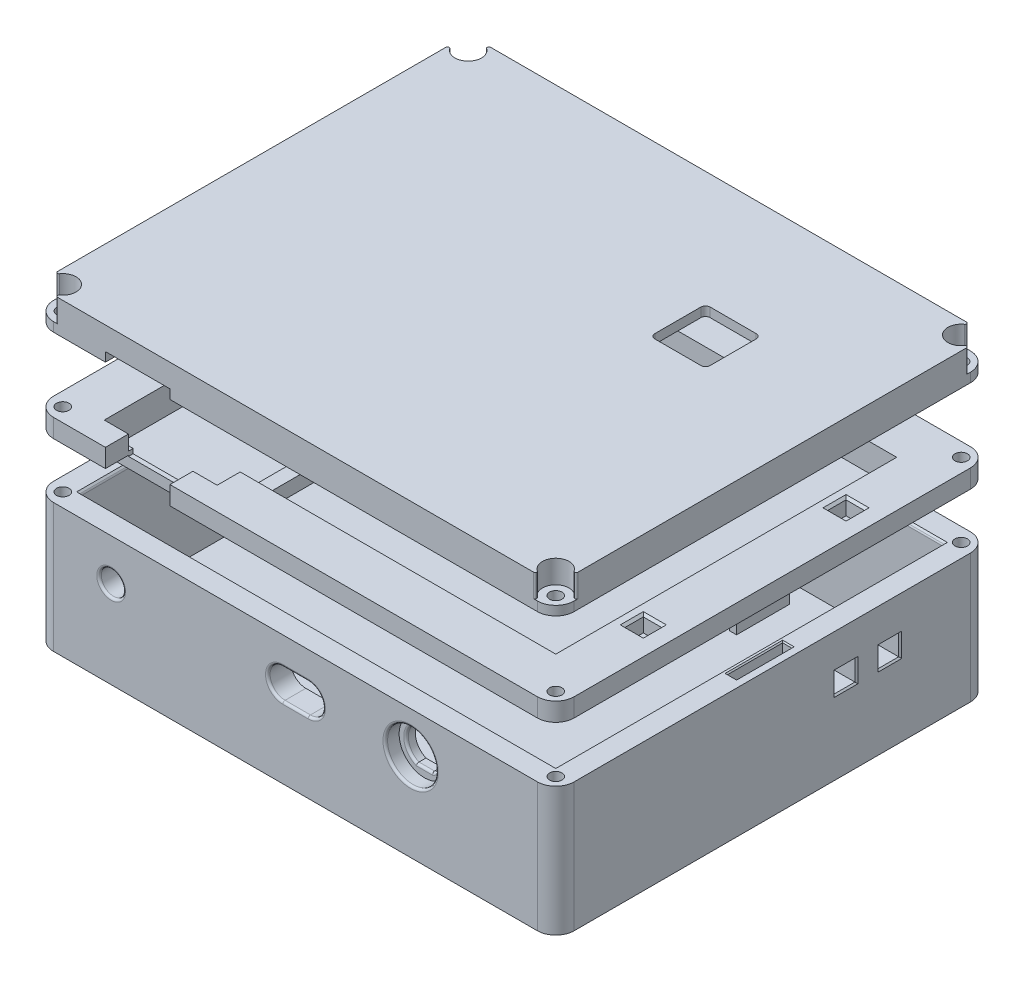
SolidWorks part; units mm, degrees
ref_plane "Front Plane" through (0, 0, 0) normal (0, 0, 1) x (1, 0, 0)
ref_plane "Top Plane" through (0, 0, 0) normal (0, 1, 0) x (1, 0, 0)
ref_plane "Right Plane" through (0, 0, 0) normal (1, 0, 0) x (0, 0, -1)
sketch "Sketch1" plane through (0, 0, 0) normal (0, 1, 0) x (1, 0, 0)
  line L0 (-1, 89) -> (104, 89)
  line L1 (0, 0) -> (103, 0)
  line L2 (0, 0) -> (0, 84)
  line L3 (0, 84) -> (103, 84)
  line L4 (103, 0) -> (103, 84)
  line L5 (108, -1) -> (108, 85)
  line L6 (-1, -5) -> (104, -5)
  line L7 (-5, -1) -> (-5, 85)
  line L8 (0, 0) -> (0, 13.5) construction
  line L9 (0, 84) -> (0, 72) construction
  line L10 (0, 0) -> (4, 0) construction
  line L11 (-5, 89) -> (108, 89) construction
  line L12 (108, -5) -> (108, 89) construction
  line L13 (-5, -5) -> (108, -5) construction
  line L14 (-5, -5) -> (-5, 89) construction
  line L15 (0, 13.5) -> (1.5, 13.5)
  line L20 (1.5, 13.5) -> (1.5, 0)
  line L21 (0, 72) -> (1.5, 72)
  line L22 (1.5, 72) -> (1.5, 84)
  line L23 (4, 0) -> (4, 1.5)
  line L24 (4, 1.5) -> (1.5, 1.5)
  arc A0 (104, 89) -> (108, 85) centre (104, 85) cw
  arc A1 (108, -1) -> (104, -5) centre (104, -1) cw
  arc A2 (-5, -1) -> (-1, -5) centre (-1, -1) ccw
  arc A3 (-5, 85) -> (-1, 89) centre (-1, 85) cw
  dimension "D7" = 4
  dimension "D1" = 103
  dimension "D2" = 84
  dimension "D4" = 13.5
  dimension "D5" = 12
  dimension "D6" = 4
  dimension "D8" = 1.5
  dimension "D9" = 1.5
  dimension "D10" = 1.5
  dimension "D3" = 5
extrude "Boss-Extrude1" add sketch "Sketch1" along normal blind 4 contours L0 A0 L5 A1 L6 A2 L7 A3
extrude "Boss-Extrude2" add sketch "Sketch1<3>" along normal blind 24 from surface contours A3 L7 A2 L6 A1 L5 A0 L0 L4 L1 L2 L3 region at (51.5, 0, -87.5301) starting at face at (51.5, 4, -42)
sketch "Sketch1<3>" plane through (0, 0, 0) normal (0, 1, 0) x (1, 0, 0) same geometry as "Sketch1"
extrude "Boss-Extrude3" add sketch "Sketch1<4>" along normal blind 8 from surface contours L21 L22 L3 L2 | L20 L15 L2 L1 | L23 L24 L20 L1 region at (0.75, 0, -6.75) region at (2.75, 0, -0.75) region at (0.75, 0, -78) starting at face at (51.5, 4, -42)
sketch "Sketch1<4>" plane through (0, 0, 0) normal (0, 1, 0) x (1, 0, 0) same geometry as "Sketch1"
chamfer "Chamfer1" distance 1 angle 45 6 edges at (0.75, 12, -13.5) (4, 12, -0.75) (2.75, 12, -1.5) (1.5, 12, -7.5) (0.75, 12, -72) (1.5, 12, -78)
sketch "Sketch2" plane through (0, 0, 0) normal (0, 0, 1) x (1, 0, 0)
  line L0 (51.5, 0) -> (51.5, 53.6645) construction
  line L1 (108, 0) -> (104, 0) construction
  line L2 (-1, 0) -> (104, 0) construction
  line L3 (-1, 0) -> (-5, 0) construction
  line L4 (108, 0) -> (104, 0) construction
  line L5 (-1, 0) -> (104, 0) construction
  line L6 (-1, 0) -> (-5, 0) construction
  line L7 (4, 4) -> (103, 4) construction
  line L8 (4, 4) -> (103, 4) construction
  line L9 (48.75, 18.7) -> (54.25, 18.7) construction
  line L10 (48.75, 21.95) -> (54.25, 21.95)
  line L11 (48.75, 15.45) -> (54.25, 15.45)
  line L12 (76.5, 4) -> (76.5, 15) construction
  line L13 (76.5, 22.625) -> (76.5, 15.375) construction
  line L14 (74.809, 22.625) -> (78.191, 22.625)
  line L15 (74.809, 15.375) -> (78.191, 15.375)
  arc A0 (48.75, 21.95) -> (48.75, 15.45) centre (48.75, 18.7) ccw
  arc A1 (54.25, 15.45) -> (54.25, 21.95) centre (54.25, 18.7) ccw
  arc A2 (74.809, 22.625) -> (74.809, 15.375) centre (76.5, 19) ccw
  circle A3 centre (76.5, 19) radius 5.5
  arc A4 (78.191, 22.625) -> (74.809, 22.625) centre (76.5, 19) ccw construction
  arc A5 (74.809, 15.375) -> (76.5, 15) centre (76.5, 19) ccw construction
  arc A6 (78.191, 15.375) -> (78.191, 22.625) centre (76.5, 19) ccw
  arc A7 (76.5, 15) -> (78.191, 15.375) centre (76.5, 19) ccw construction
  circle A8 centre (11.5, 19) radius 2.625
  point P6 (51.5, 18.7)
  point P15 (45.5, 18.7)
  point P16 (57.5, 18.7)
  point P26 (76.5, 19)
  point P28 (76.5, 22.625)
  point P31 (76.5, 15.375)
  dimension "D5" = 8
  dimension "D6" = 11
  dimension "D3" = 5.25
  dimension "D1" = 12
  dimension "D2" = 6.5
  dimension "D4" = 11
  dimension "D7" = 25
  dimension "D8" = 7.25
  dimension "D9" = 14.7
  dimension "D10" = 40
  dimension "D11" = 15
extrude "Cut-Extrude1" cut sketch "Sketch2" along normal blind 11 contours L11 A1 L10 A0 | L15 A6 L14 A2 | A8 region at (51.5, 18.7, 0) region at (76.5, 19, 0) region at (11.5, 19, 0)
extrude "Cut-Extrude2" cut sketch "Sketch2<3>" against normal blind 3 from surface contours A3 starting at face at (8.875, 19, 5)
sketch "Sketch2<3>" plane through (0, 0, 0) normal (0, 0, 1) x (1, 0, 0) same geometry as "Sketch2"
chamfer "Chamfer2" distance 0.5 angle 45 4 edges at (103, 28, -42) (51.5, 28, 0) (0, 28, -42) (51.5, 28, -84)
fillet "Fillet1" [suppressed] radius 5
fillet "Fillet2" radius 0.5 10 edges at (51.5, 21.95, 5) (57.5, 18.7, 5) (51.5, 15.45, 5) (71, 19, 5) (80.5, 19, 2) (76.5, 22.625, 2) (76.5, 15.375, 2) (72.5, 19, 2) (45.5, 18.7, 5) (8.875, 19, 5)
sketch "Sketch3" plane through (0, 28, 0) normal (0, 1, 0) x (1, 0, 0)
  line L0 (103, 0) -> (103, 84) construction
  line L1 (0, 0) -> (103, 0) construction
  line L2 (0, 0) -> (0, 84) construction
  line L3 (0, 84) -> (103, 84) construction
  line L4 (103, 0) -> (103, 84) construction
  line L5 (0, 0) -> (103, 0) construction
  line L6 (0, 0) -> (0, 84) construction
  line L7 (0, 84) -> (103, 84) construction
  line L8 (105, -2) -> (105, 86) construction
  line L9 (-2, 86) -> (105, 86) construction
  line L10 (-2, -2) -> (-2, 86) construction
  line L11 (-2, -2) -> (105, -2) construction
  line L12 (51.5, 86) -> (51.5, -2) construction
  line L13 (-1.25, 48) -> (-3.25, 48)
  line L14 (-1.25, 48) -> (-1.25, 36)
  line L15 (-1.25, 36) -> (-3.25, 36)
  line L16 (-3.25, 48) -> (-3.25, 36)
  line L17 (-1.25, 48) -> (-3.25, 36) construction
  line L18 (-1.25, 36) -> (-3.25, 48) construction
  line L19 (104.25, 36) -> (106.25, 36)
  line L20 (106.25, 48) -> (106.25, 36)
  line L21 (104.25, 48) -> (106.25, 48)
  line L22 (104.25, 48) -> (104.25, 36)
  circle A0 centre (-2, 86) radius 1.35
  circle A1 centre (105, 86) radius 1.35
  circle A2 centre (105, -2) radius 1.35
  circle A3 centre (-2, -2) radius 1.35
  point P12 (-2.25, 42)
  point P25 (-2, 42)
  dimension "D2" = 2.7
  dimension "D3" = 2.7
  dimension "D4" = 2.7
  dimension "D5" = 2.7
  dimension "D6" = 2
  dimension "D7" = 12
  dimension "D8" = 0.25
  dimension "D1" = 2
extrude "Cut-Extrude3" cut sketch "Sketch3" against normal blind 8 contours A3 | A2 | A1 | A0 region at (-2, 28, -86) region at (105, 28, -86) region at (105, 28, 2) region at (-2, 28, 2)
extrude "Cut-Extrude12" cut sketch "Sketch3<3>" against normal blind 4 contours L15 L16 L13 L14 | L19 L20 L21 L22
sketch "Sketch3<3>" plane through (0, 28, 0) normal (0, 1, 0) x (1, 0, 0) same geometry as "Sketch3"
ref_plane "Plane1" through (0, 40, 0) normal (0, 1, 0) x (1, 0, 0)
sketch "Sketch4" plane through (0, 40, 0) normal (0, 1, 0) x (1, 0, 0)
  line L4 (0, 0) -> (103, 0)
  line L5 (103, 0) -> (103, 84)
  line L6 (103, 84) -> (0, 84)
  line L7 (0, 84) -> (0, 0)
  line L8 (0, 0) -> (103, 0)
  line L9 (103, 0) -> (103, 84)
  line L10 (103, 84) -> (0, 84)
  line L11 (0, 84) -> (0, 0)
  line L12 (104, 89) -> (-1, 89)
  line L13 (108, -1) -> (108, 85)
  line L14 (-1, -5) -> (104, -5)
  line L15 (-5, 85) -> (-5, -1)
  line L16 (104, 89) -> (-1, 89)
  line L17 (108, -1) -> (108, 85)
  line L18 (-1, -5) -> (104, -5)
  line L19 (-5, 85) -> (-5, -1)
  line L23 (98, 79) -> (5, 79)
  line L25 (5, 79) -> (5, 5)
  line L26 (5, 5) -> (98, 5)
  line L28 (98, 5) -> (98, 79)
  line L29 (104.25, 36) -> (106.25, 36)
  line L30 (106.25, 36) -> (106.25, 48)
  line L31 (106.25, 48) -> (104.25, 48)
  line L32 (104.25, 48) -> (104.25, 36)
  line L33 (104.25, 36) -> (106.25, 36)
  line L34 (106.25, 36) -> (106.25, 48)
  line L35 (106.25, 48) -> (104.25, 48)
  line L36 (104.25, 48) -> (104.25, 36)
  line L37 (-1.25, 48) -> (-3.25, 48)
  line L38 (-1.25, 36) -> (-1.25, 48)
  line L39 (-3.25, 36) -> (-1.25, 36)
  line L40 (-3.25, 48) -> (-3.25, 36)
  line L41 (-1.25, 48) -> (-3.25, 48)
  line L42 (-1.25, 36) -> (-1.25, 48)
  line L43 (-3.25, 36) -> (-1.25, 36)
  line L44 (-3.25, 48) -> (-3.25, 36)
  line L45 (-1.5, 47.75) -> (-3, 47.75)
  line L46 (-3, 47.75) -> (-3, 36.25)
  line L47 (-3, 36.25) -> (-1.5, 36.25)
  line L48 (-1.5, 36.25) -> (-1.5, 47.75)
  line L49 (104.5, 36.25) -> (106, 36.25)
  line L50 (106, 36.25) -> (106, 47.75)
  line L51 (106, 47.75) -> (104.5, 47.75)
  line L52 (104.5, 47.75) -> (104.5, 36.25)
  line L53 (5, 5) -> (5, 0)
  line L54 (29.5, 5) -> (29.5, 0)
  circle A1 centre (-2, -2) radius 1.35
  circle A2 centre (-2, -2) radius 1.35
  circle A3 centre (105, -2) radius 1.35
  arc A4 (108, 85) -> (104, 89) centre (104, 85) ccw
  arc A5 (104, -5) -> (108, -1) centre (104, -1) ccw
  arc A6 (-5, -1) -> (-1, -5) centre (-1, -1) ccw
  arc A7 (-1, 89) -> (-5, 85) centre (-1, 85) ccw
  arc A8 (108, 85) -> (104, 89) centre (104, 85) ccw
  arc A9 (104, -5) -> (108, -1) centre (104, -1) ccw
  arc A10 (-5, -1) -> (-1, -5) centre (-1, -1) ccw
  arc A11 (-1, 89) -> (-5, 85) centre (-1, 85) ccw
  circle A12 centre (105, -2) radius 1.35
  circle A13 centre (105, 86) radius 1.35
  circle A14 centre (105, 86) radius 1.35
  circle A15 centre (-2, 86) radius 1.35
  circle A16 centre (-2, 86) radius 1.35
  dimension "D11" = 24.5
  dimension "D1" = 0
  dimension "D2" = 0
  dimension "D3" = 0
  dimension "D4" = 0
  dimension "D5" = 0
  dimension "D6" = 0
  dimension "D7" = 0
  dimension "D8" = 0
  dimension "D9" = 5
  dimension "D10" = 0.25
extrude "Boss-Extrude4" add sketch "Sketch4" along normal blind 4 separate body contours L16 A11 L19 A10 L18 A9 L17 A8 A16 A14 A12 L11 L10 L9 L8 L36 L35 L34 L33 L44 L41 L42 L43 A2 | L41 L44 L43 L42 | L35 L36 L33 L34 region at (106.7245, 40, -87.7245)
extrude "Boss-Extrude7" add sketch "Sketch4<5>" against normal blind 4 contours L46 L47 L48 L45 | L50 L51 L52 L49
sketch "Sketch4<5>" plane through (0, 40, 0) normal (0, 1, 0) x (1, 0, 0) same geometry as "Sketch4"
extrude "Boss-Extrude5" add sketch "Sketch4<3>" along normal mid plane 8 contours L10 L11 L8 L9 L28 L26 L25 L23 region at (1.3291, 40, -42)
sketch "Sketch4<3>" plane through (0, 40, 0) normal (0, 1, 0) x (1, 0, 0) same geometry as "Sketch4"
extrude "Boss-Extrude6" add sketch "Sketch4<4>" along normal blind 2 from surface contours L23 L25 L26 L28 starting at face at (47.1, 36, -33.6)
sketch "Sketch4<4>" plane through (0, 40, 0) normal (0, 1, 0) x (1, 0, 0) same geometry as "Sketch4"
sketch "Sketch5" plane through (0, 0, -5) normal (0, 0, 1) x (1, 0, 0)
  line L4 (5, 36) -> (29.5, 36)
  line L5 (29.5, 36) -> (29.5, 38)
  line L6 (29.5, 38) -> (5, 38)
  line L7 (5, 38) -> (5, 36)
  line L8 (5, 36) -> (29.5, 36)
  line L9 (29.5, 36) -> (29.5, 38)
  line L10 (29.5, 38) -> (5, 38)
  line L11 (5, 38) -> (5, 36)
  dimension "D1" = 0
extrude "Boss-Extrude8" add sketch "Sketch5" along normal up to surface (5 mm away) up to face at (2.5, 38, 0)
chamfer "Chamfer3" distance 1.5 angle 45 4 edges at (103, 36, -42) (51.5, 36, -84) (51.5, 36, 0) (0, 36, -42)
sketch "Sketch7" plane through (0, 0, 0) normal (0, 0, 1) x (1, 0, 0)
  line L0 (29.5, 40) -> (29.5, 38) construction
  line L2 (5, 40) -> (5, 38) construction
  line L3 (29.5, 40.7937) -> (29.5, 37.7398)
  line L4 (5, 37.7398) -> (29.5, 37.7398)
  line L5 (5, 40.7937) -> (5, 37.7398)
  line L6 (5, 40.7937) -> (29.5, 40.7937)
extrude "Boss-Extrude11" add sketch "Sketch7" against normal blind 1
sketch "Sketch6" plane through (0, 0, 0) normal (0, 0, 1) x (1, 0, 0)
  line L0 (5, 38) -> (29.5, 38) construction
  line L1 (5, 38) -> (29.5, 38) construction
  line L2 (17.25, 38) -> (17.25, 44.8184) construction
  line L3 (10.25, 39.8) -> (24.25, 39.8)
  line L4 (10.25, 41.5) -> (24.25, 41.5)
  line L5 (0, 37.5) -> (103, 37.5) construction
  line L6 (10.25, 41.5) -> (10.25, 39.8)
  line L7 (24.25, 41.5) -> (24.25, 39.8)
  line L8 (10.25, 41.5) -> (10.25, 44.8184)
  line L9 (10.25, 44.8184) -> (24.25, 44.8184)
  line L10 (24.25, 44.8184) -> (24.25, 41.5)
  point P7 (17.25, 39.8)
  point P10 (17.25, 41.5)
  dimension "D1" = 14
  dimension "D2" = 1.8
  dimension "D3" = 14
  dimension "D4" = 4
extrude "Cut-Extrude4" cut sketch "Sketch6" along normal mid plane 15 contours L10 L9 L8 L4 | L7 L3 L6 L4 region at (17.25, 43.1592, 0)
sketch "Sketch8" plane through (0, 38, 0) normal (0, 1, 0) x (1, 0, 0)
  line L0 (5, 44) -> (29.5, 44)
  line L1 (5, 79) -> (5, 1) construction
  line L2 (29.5, 1) -> (5, 1) construction
  line L3 (29.5, 44) -> (29.5, 5)
  line L4 (5, 48) -> (33.5, 48)
  line L5 (33.5, 48) -> (33.5, 5)
  line L7 (9.25, 52) -> (25.25, 52)
  line L8 (9.25, 52) -> (9.25, 56)
  line L9 (9.25, 56) -> (25.25, 56)
  line L10 (25.25, 52) -> (25.25, 56)
  point P16 (17.25, 52)
  point P17 (17.25, 44)
  line M11 (29.5, 5) -> (98, 5)
  line M14 (5, 79) -> (5, 1)
  dimension "D1" = 43
  dimension "D2" = 24.5
  dimension "D3" = 4
  dimension "D4" = 4
  dimension "D5" = 4
  dimension "D6" = 16
  dimension "D7" = 4
extrude "Boss-Extrude12" add sketch "Sketch8" along normal blind 3 contours L5 L4 L0 L3 M14 M11 region at (5.5159, 38, -46)
extrude "Cut-Extrude5" cut sketch "Sketch8<3>" against normal blind 3.5 contours L9 L10 L7 L8
sketch "Sketch8<3>" plane through (0, 38, 0) normal (0, 1, 0) x (1, 0, 0) same geometry as "Sketch8"
chamfer "Chamfer4" distance 1 angle 45 6 edges at (25.25, 38, -54) (17.25, 38, -56) (9.25, 38, -54) (17.25, 38, -52) (29.5, 41, -24.5) (17.25, 41, -44)
sketch "Sketch10" plane through (0, 38, 0) normal (0, 1, 0) x (1, 0, 0)
  line L0 (77.5, 64) -> (77.5, 52) construction
  line L1 (73.5, 64) -> (81.5, 64)
  line L2 (71.5, 62) -> (71.5, 54)
  line L3 (73.5, 52) -> (81.5, 52)
  line L4 (83.5, 62) -> (83.5, 54)
  line L5 (73.7129, 58) -> (81.5, 58) construction
  line L6 (82.5, 61.375) -> (84.5, 61.375)
  line L7 (82.5, 61.375) -> (82.5, 59.625)
  line L8 (82.5, 59.625) -> (84.5, 59.625)
  line L9 (84.5, 61.375) -> (84.5, 59.625)
  line L10 (82.5, 61.375) -> (84.5, 59.625) construction
  line L11 (82.5, 59.625) -> (84.5, 61.375) construction
  line L12 (82.5, 56.375) -> (84.5, 56.375)
  line L13 (84.5, 54.625) -> (84.5, 56.375)
  line L14 (82.5, 54.625) -> (84.5, 54.625)
  line L15 (82.5, 54.625) -> (82.5, 56.375)
  line L16 (72.5, 59.625) -> (70.5, 59.625)
  line L17 (70.5, 61.375) -> (70.5, 59.625)
  line L18 (72.5, 61.375) -> (70.5, 61.375)
  line L19 (72.5, 61.375) -> (72.5, 59.625)
  line L20 (72.5, 54.625) -> (72.5, 56.375)
  line L21 (72.5, 54.625) -> (70.5, 54.625)
  line L22 (70.5, 54.625) -> (70.5, 56.375)
  line L23 (72.5, 56.375) -> (70.5, 56.375)
  line L24 (51.5, 89) -> (51.5, -5) construction
  line L25 (-1, 89) -> (104, 89) construction
  line L26 (-1, -5) -> (104, -5) construction
  line L27 (-5, 42) -> (108, 42) construction
  line L28 (-5, -1) -> (-5, 85) construction
  line L29 (108, -1) -> (108, 85) construction
  line L30 (3, 18) -> (3, 22)
  line L31 (-1, 66) -> (3, 66)
  line L32 (-1, 66) -> (-1, 62)
  line L33 (-1, 62) -> (3, 62)
  line L34 (3, 66) -> (3, 62)
  line L35 (-1, 22) -> (3, 22)
  line L36 (-1, 18) -> (-1, 22)
  line L37 (-1, 18) -> (3, 18)
  line L39 (100, 18) -> (100, 22)
  line L40 (104, 18) -> (100, 18)
  line L41 (104, 18) -> (104, 22)
  line L42 (104, 22) -> (100, 22)
  line L43 (104, 62) -> (100, 62)
  line L44 (100, 66) -> (100, 62)
  line L45 (104, 66) -> (104, 62)
  line L46 (104, 66) -> (100, 66)
  circle A0 centre (77.5, 62.35) radius 0.8
  circle A1 centre (77.5, 53.65) radius 0.8
  arc A2 (71.5, 54) -> (73.5, 52) centre (73.5, 54) ccw
  arc A3 (81.5, 52) -> (83.5, 54) centre (81.5, 54) ccw
  arc A4 (83.5, 62) -> (81.5, 64) centre (81.5, 62) ccw
  arc A5 (71.5, 62) -> (73.5, 64) centre (73.5, 62) cw
  point P10 (77.5, 58)
  point P13 (71.5, 52)
  point P16 (83.5, 52)
  point P21 (71.5, 64)
  point P22 (83.5, 60.5)
  dimension "D3" = 1.6
  dimension "D4" = 1.6
  dimension "D7" = 2
  dimension "D1" = 12
  dimension "D2" = 12
  dimension "D5" = 8.7
  dimension "D6" = 4.35
  dimension "D8" = 1.75
  dimension "D9" = 2
  dimension "D10" = 2.5
  dimension "D11" = 4
  dimension "D12" = 4
  dimension "D13" = 20
  dimension "D14" = 48.5
  dimension "D15" = 20
  dimension "D16" = 10
extrude "Cut-Extrude6" cut sketch "Sketch10" against normal blind 3.5 from surface contours L36 L37 L30 L35 | L41 L42 L39 L40 | L45 L46 L44 L43 | L34 L31 L32 L33 region at (1, 38, -20) region at (1, 38, -64) region at (102, 38, -20) region at (102, 38, -64) starting at face at (41.4444, 44, -27.4444)
extrude "Boss-Extrude13" add sketch "Sketch10<3>" along normal blind 1.5 contours A5 L2 L18 L19 L16 L23 L20 L21 A2 L3 A3 L4 L14 L15 L12 L8 L7 L6 A4 L1 A1 A0 region at (77.5, 38, -58)
sketch "Sketch10<3>" plane through (0, 38, 0) normal (0, 1, 0) x (1, 0, 0) same geometry as "Sketch10"
extrude "Cut-Extrude7" cut sketch "Sketch10<4>" against normal up to next (2 mm away) contours L9 L6 L4 L8 | L7 L8 L4 L6 | L4 L14 L13 L12 | L15 L14 L4 L12 | L20 L23 L2 L21 | L2 L23 L22 L21 | L19 L18 L2 L16 | L17 L16 L19 L18 region at (72, 38, -60.5) region at (84, 38, -60.5) region at (83, 38, -60.5) region at (72, 38, -55.5) region at (71, 38, -55.5) region at (84, 38, -55.5) region at (83, 38, -55.5)
sketch "Sketch10<4>" plane through (0, 38, 0) normal (0, 1, 0) x (1, 0, 0) same geometry as "Sketch10"
fillet "Fillet3" radius 0.5 2 edges at (77.5, 39.5, -52.85) (77.5, 39.5, -61.55)
chamfer "Chamfer5" distance 0.5 angle 45 16 edges at (104, 44, -64) (102, 44, -62) (100, 44, -64) (102, 44, -66) (104, 44, -20) (102, 44, -18) (100, 44, -20) (102, 44, -22) (3, 44, -20) (1, 44, -18) (-1, 44, -20) (1, 44, -22) (1, 44, -62) (3, 44, -64) (-1, 44, -64) (1, 44, -66)
ref_plane "Plane3" through (0, 60, 0) normal (0, 1, 0) x (1, 0, 0)
sketch "Sketch12" plane through (0, 60, 0) normal (0, 1, 0) x (1, 0, 0)
  line L0 (29.5, 5) -> (5, 5)
  line L1 (24.25, -5) -> (10.25, -5)
  line L2 (100, 66) -> (100, 62) construction
  line L7 (72.5, 64) -> (82.5, 64)
  line L8 (71.5, 63) -> (71.5, 53)
  line L9 (72.5, 52) -> (82.5, 52)
  line L10 (83.5, 63) -> (83.5, 53)
  line L11 (71.5, 64) -> (83.5, 52) construction
  line L12 (71.5, 52) -> (83.5, 64) construction
  line L13 (100, 62) -> (104, 62) construction
  line L14 (24.25, 0) -> (24.25, -5)
  line L15 (24.25, -5) -> (104, -5)
  line L16 (108, -1) -> (108, 85)
  line L17 (104, 89) -> (-1, 89)
  line L18 (-5, 85) -> (-5, -1)
  line L19 (-1, -5) -> (10.25, -5)
  line L20 (10.25, -5) -> (10.25, 0)
  line L21 (10.25, 0) -> (5, 0)
  line L22 (5, 0) -> (5, 79)
  line L23 (5, 79) -> (98, 79)
  line L24 (98, 79) -> (98, 5)
  line L25 (98, 5) -> (29.5, 5)
  line L26 (29.5, 5) -> (29.5, 0)
  line L27 (29.5, 0) -> (24.25, 0)
  line L28 (24.25, 0) -> (24.25, -5)
  line L29 (24.25, -5) -> (104, -5)
  line L30 (108, -1) -> (108, 85)
  line L31 (104, 89) -> (-1, 89)
  line L32 (-5, 85) -> (-5, -1)
  line L33 (-1, -5) -> (10.25, -5)
  line L34 (10.25, -5) -> (10.25, 0)
  line L35 (10.25, 0) -> (5, 0)
  line L36 (5, 0) -> (5, 79)
  line L37 (5, 79) -> (98, 79)
  line L38 (98, 79) -> (98, 5)
  line L39 (98, 5) -> (29.5, 5)
  line L40 (29.5, 5) -> (29.5, 0)
  line L41 (29.5, 0) -> (24.25, 0)
  line L42 (104, 62) -> (104, 66) construction
  line L43 (104, 66) -> (100, 66) construction
  line L44 (100, 18) -> (104, 18) construction
  line L45 (104, 18) -> (104, 22) construction
  line L46 (104, 22) -> (100, 22) construction
  line L47 (100, 22) -> (100, 18) construction
  line L48 (3, 18) -> (3, 22) construction
  line L49 (3, 22) -> (-1, 22) construction
  line L62 (-1, 22) -> (-1, 18) construction
  line L63 (-1, 18) -> (3, 18) construction
  line L64 (-1, 62) -> (3, 62) construction
  line L65 (3, 62) -> (3, 66) construction
  line L66 (3, 66) -> (-1, 66) construction
  line L67 (-1, 66) -> (-1, 62) construction
  line L68 (100, 66) -> (100, 62) construction
  line L69 (100, 62) -> (104, 62) construction
  line L70 (104, 62) -> (104, 66) construction
  line L71 (104, 66) -> (100, 66) construction
  line L72 (100, 18) -> (104, 18) construction
  line L73 (104, 18) -> (104, 22) construction
  line L74 (104, 22) -> (100, 22) construction
  line L75 (100, 22) -> (100, 18) construction
  line L76 (3, 18) -> (3, 22) construction
  line L77 (3, 22) -> (-1, 22) construction
  line L78 (-1, 22) -> (-1, 18) construction
  line L79 (-1, 18) -> (3, 18) construction
  line L80 (-1, 62) -> (3, 62) construction
  line L81 (3, 62) -> (3, 66) construction
  line L82 (3, 66) -> (-1, 66) construction
  line L83 (-1, 66) -> (-1, 62) construction
  line L84 (-0.65, 62.35) -> (2.65, 62.35)
  line L85 (2.65, 62.35) -> (2.65, 65.65)
  line L86 (2.65, 65.65) -> (-0.65, 65.65)
  line L87 (-0.65, 65.65) -> (-0.65, 62.35)
  line L88 (2.65, 18.35) -> (2.65, 21.65)
  line L89 (2.65, 21.65) -> (-0.65, 21.65)
  line L90 (-0.65, 21.65) -> (-0.65, 18.35)
  line L91 (-0.65, 18.35) -> (2.65, 18.35)
  line L92 (100.35, 18.35) -> (103.65, 18.35)
  line L93 (103.65, 18.35) -> (103.65, 21.65)
  line L94 (103.65, 21.65) -> (100.35, 21.65)
  line L95 (100.35, 21.65) -> (100.35, 18.35)
  line L96 (100.35, 65.65) -> (100.35, 62.35)
  line L97 (100.35, 62.35) -> (103.65, 62.35)
  line L98 (103.65, 62.35) -> (103.65, 65.65)
  line L99 (103.65, 65.65) -> (100.35, 65.65)
  arc A0 (83.5, 63) -> (82.5, 64) centre (82.5, 63) ccw
  arc A1 (83.5, 53) -> (82.5, 52) centre (82.5, 53) cw
  arc A2 (71.5, 53) -> (72.5, 52) centre (72.5, 53) ccw
  arc A3 (71.5, 63) -> (72.5, 64) centre (72.5, 63) cw
  arc A4 (104, -5) -> (108, -1) centre (104, -1) ccw
  arc A5 (108, 85) -> (104, 89) centre (104, 85) ccw
  arc A6 (-1, 89) -> (-5, 85) centre (-1, 85) ccw
  arc A7 (-5, -1) -> (-1, -5) centre (-1, -1) ccw
  arc A8 (104, -5) -> (108, -1) centre (104, -1) ccw
  arc A9 (108, 85) -> (104, 89) centre (104, 85) ccw
  arc A10 (-1, 89) -> (-5, 85) centre (-1, 85) ccw
  arc A11 (-5, -1) -> (-1, -5) centre (-1, -1) ccw
  point P4 (77.5, 58)
  dimension "D3" = 1
  dimension "D2" = 12
  dimension "D1" = 0
  dimension "D4" = 0.35
extrude "Boss-Extrude14" add sketch "Sketch12" along normal blind 5 separate body contours L32 A11 L33 L34 L35 L36 L37 L38 L39 L40 L41 L28 L29 A8 L30 A9 L31 A10 | L41 L40 L0 L36 L35 L34 L1 L28 | L86 L87 L84 L85 | L90 L91 L88 L89 | L94 L95 L92 L93 | L98 L99 L96 L97 region at (17.25, 60, -0.6818) region at (63.75, 60, -3.5301) region at (1, 60, -64) region at (1, 60, -20) region at (102, 60, -20) region at (102, 60, -64)
sketch "Sketch13" plane through (0, 0, 5) normal (0, 0, 1) x (1, 0, 0)
  line L0 (10.25, 60) -> (24.25, 60)
  line L1 (24.25, 60) -> (24.25, 62)
  line L2 (24.25, 62) -> (10.25, 62)
  line L3 (10.25, 62) -> (10.25, 60)
  dimension "D1" = 2
extrude "Cut-Extrude8" cut sketch "Sketch13" against normal up to next (10 mm away)
extrude "Boss-Extrude15" add sketch "Sketch12<3>" along normal blind 2 from surface contours L39 L38 L37 L36 L0 L8 A3 L7 A0 L10 A1 L9 A2 | L32 A11 L33 L34 L35 L36 L37 L38 L39 L40 L41 L28 L29 A8 L30 A9 L31 A10 L87 L86 L85 L84 L91 L90 L89 L88 L95 L94 L93 L92 L99 L98 L97 L96 | L41 L40 L0 L36 L35 L34 L1 L28 | L90 L91 L88 L89 | L86 L87 L84 L85 | L98 L99 L96 L97 | L94 L95 L92 L93 region at (17.25, 60, -0.6818) region at (50.9477, 60, -41.6601) region at (63.75, 60, -3.5301) region at (1, 60, -64) region at (1, 60, -20) region at (102, 60, -20) region at (102, 60, -64) starting at face at (51.5, 65, -42)
sketch "Sketch12<3>" plane through (0, 60, 0) normal (0, 1, 0) x (1, 0, 0) same geometry as "Sketch12"
sketch "Sketch14" plane through (0, 60, 0) normal (0, 1, 0) x (1, 0, 0)
  circle A0 centre (-2, 86) radius 1.35 construction
  circle A1 centre (105, 86) radius 1.35 construction
  circle A2 centre (105, -2) radius 1.35 construction
  circle A3 centre (-2, -2) radius 1.35 construction
  circle A4 centre (-2, 86) radius 1.35
  circle A5 centre (105, 86) radius 1.35
  circle A6 centre (105, -2) radius 1.35
  circle A7 centre (-2, -2) radius 1.35
  circle A8 centre (-2, -2) radius 2.875
  circle A9 centre (-2, 86) radius 2.875
  circle A10 centre (105, 86) radius 2.875
  circle A11 centre (105, -2) radius 2.875
  dimension "D1" = 5.75
  dimension "D2" = 5.75
  dimension "D3" = 5.75
  dimension "D4" = 5.75
extrude "Cut-Extrude9" cut sketch "Sketch14" along normal up to next (7 mm away) contours A4 | A5 | A6 | A7
extrude "Cut-Extrude10" cut sketch "Sketch14<3>" along normal blind 5 from offset 2 contours A9 | A10 | A8 | A11
sketch "Sketch14<3>" plane through (0, 60, 0) normal (0, 1, 0) x (1, 0, 0) same geometry as "Sketch14"
fillet "Fillet4" radius 0.35 8 edges at (-1.9922, 64.5, -88.875) (-4.875, 64.5, -85.9922) (107.875, 64.5, -85.9922) (104.9922, 64.5, -88.875) (104.9922, 64.5, 4.875) (107.875, 64.5, 1.9922) (-1.9922, 64.5, 4.875) (-4.875, 64.5, 1.9922)
sketch "Sketch17" plane through (0, 0, -89) normal (0, 0, -1) x (-1, 0, 0)
  line L0 (-1.5, 4) -> (-103, 4) construction
  line L1 (-1.5, 4) -> (-103, 4) construction
  line L2 (-52.25, 4) -> (-52.25, 34.8114) construction
  line L3 (-68.25, 24) -> (-68.25, 14) construction
  line L4 (-73.25, 19) -> (-63.25, 19) construction
  circle A0 centre (-68.25, 19) radius 5
  circle A1 centre (-68.25, 19) radius 6
  dimension "D3" = 10
  dimension "D4" = 12
  dimension "D1" = 10
  dimension "D2" = 21
extrude "Cut-Extrude11" cut sketch "Sketch17" against normal blind 5 contours A0 region at (68.25, 19, -89)
chamfer "Chamfer6" distance 0.25 angle 45 8 edges at (106.25, 28, -42) (105.25, 28, -48) (104.25, 28, -42) (105.25, 28, -36) (-2.25, 28, -36) (-1.25, 28, -42) (-2.25, 28, -48) (-3.25, 28, -42)
fillet "Fillet5" radius 1 2 edges at (63.25, 19, -89) (63.25, 19, -84)
fillet "Fillet6" radius 0.5 4 edges at (51.5, 27.5, 0) (103, 27.5, -42) (51.5, 27.5, -84) (0, 27.5, -42)
sketch "Sketch18" plane through (103, 0, 0) normal (-1, 0, 0) x (0, 0, 1)
  line L0 (-58, 34.8792) -> (-58, 37.0792) construction
  line L1 (-60, 20.2137) -> (-56, 20.2137)
  line L2 (-60, 20.2137) -> (-60, 16.2137)
  line L3 (-60, 16.2137) -> (-56, 16.2137)
  line L4 (-56, 20.2137) -> (-56, 16.2137)
  line L5 (-60, 20.2137) -> (-56, 16.2137) construction
  line L6 (-60, 16.2137) -> (-56, 20.2137) construction
  line L12 (-67.5, 18.2137) -> (-58, 18.2137) construction
  line L17 (-60.25, 20.4637) -> (-55.75, 20.4637)
  line L18 (-55.75, 20.4637) -> (-55.75, 15.9637)
  line L19 (-60.25, 15.9637) -> (-55.75, 15.9637)
  line L20 (-60.25, 20.4637) -> (-60.25, 15.9637)
  line L21 (-69.5, 20.2137) -> (-65.5, 20.2137)
  line L22 (-69.5, 20.2137) -> (-69.5, 16.2137)
  line L23 (-69.5, 16.2137) -> (-65.5, 16.2137)
  line L24 (-65.5, 20.2137) -> (-65.5, 16.2137)
  line L25 (-69.5, 20.2137) -> (-65.5, 16.2137) construction
  line L26 (-69.5, 16.2137) -> (-65.5, 20.2137) construction
  line L27 (-69.75, 20.4637) -> (-65.25, 20.4637)
  line L28 (-65.25, 20.4637) -> (-65.25, 15.9637)
  line L29 (-69.75, 15.9637) -> (-65.25, 15.9637)
  line L30 (-69.75, 20.4637) -> (-69.75, 15.9637)
  point P0 (-58, 18.2137)
  point P21 (-67.5, 18.2137)
  point P31 (-67.5, 20.4637)
  dimension "D1" = 4
  dimension "D2" = 4
  dimension "D8" = 4
  dimension "D9" = 4
  dimension "D10" = 0.25
  dimension "D11" = 0.25
  dimension "D12" = 5
  dimension "D13" = 0.25
  dimension "D14" = 0.25
  dimension "D7" = 0.25
extrude "Cut-Extrude13" cut sketch "Sketch18" against normal up to surface (5 mm away) contours L17 L20 L19 L18 L1 L4 L3 L2 | L4 L1 L2 L3 | L24 L21 L22 L23 | L27 L30 L29 L28 L21 L24 L23 L22 region at (103, 18.2137, -58) region at (103, 20.4001, -58) region at (103, 18.2137, -67.5) region at (103, 20.4001, -67.5) up to face at (108, 14, -42)
chamfer "Chamfer7" distance 0.325 angle 45 16 edges at (108, 20.4637, -58) (108, 18.2137, -55.75) (108, 15.9637, -58) (108, 18.2137, -60.25) (103, 18.2137, -55.75) (103, 20.4637, -58) (103, 18.2137, -60.25) (103, 15.9637, -58) (108, 18.2137, -65.25) (108, 20.4637, -67.5) (108, 15.9637, -67.5) (108, 18.2137, -69.75) (103, 18.2137, -65.25) (103, 20.4637, -67.5) (103, 18.2137, -69.75) (103, 15.9637, -67.5)
